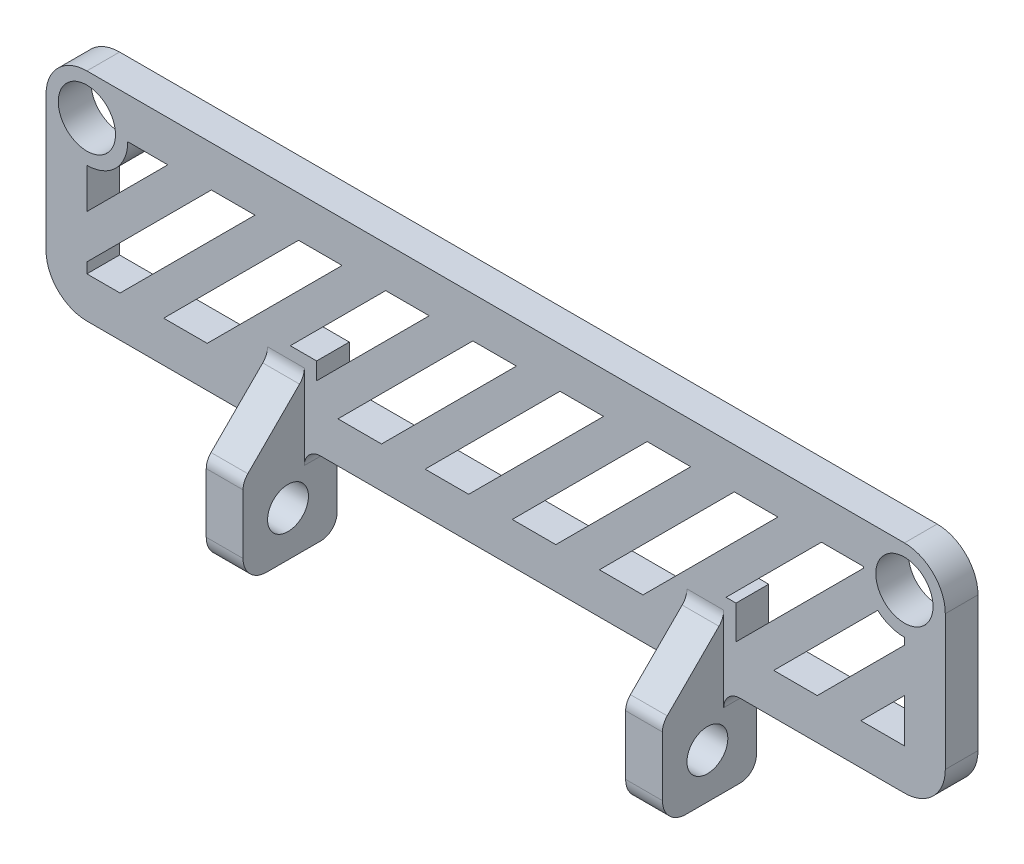
SolidWorks part; units mm, degrees
ref_plane "Plan de face" through (0, 0, 0) normal (0, 0, 1) x (1, 0, 0)
ref_plane "Plan de dessus" through (0, 0, 0) normal (0, 1, 0) x (1, 0, 0)
ref_plane "Plan de droite" through (0, 0, 0) normal (1, 0, 0) x (0, 0, -1)
sketch "Esquisse1" plane through (0, 0, 0) normal (0, 0, 1) x (1, 0, 0)
  line L0 (-25, 6.875) -> (-27.5, 6.875) construction
  line L1 (-27.5, 9.375) -> (27.5, 9.375)
  line L2 (-27.5, 9.375) -> (-27.5, -9.375)
  line L3 (-27.5, -9.375) -> (27.5, -9.375)
  line L4 (27.5, 9.375) -> (27.5, -9.375)
  line L5 (25, 6.875) -> (27.5, 6.875) construction
  line L6 (-25, 6.875) -> (-25, 9.375) construction
  line L7 (25, 6.875) -> (25, 9.375) construction
  line L8 (0, 0) -> (27.5, 0) construction
  line L9 (-13.95, -9.375) -> (-13.95, -3.875)
  line L10 (-13.95, -3.875) -> (13.95, -3.875)
  line L11 (13.95, -3.875) -> (13.95, -9.375)
  line L12 (-11.7, -3.875) -> (-11.7, -9.375)
  line L13 (11.7, -3.875) -> (11.7, -9.375)
  line L14 (-13.95, -6.625) -> (-11.7, -6.625) construction
  line L15 (11.7, -6.625) -> (13.95, -6.625) construction
  circle A0 centre (-25, 6.875) radius 1.75
  circle A1 centre (25, 6.875) radius 1.75
  circle A2 centre (-25, -6.875) radius 1.75 construction
  circle A3 centre (25, -6.875) radius 1.75 construction
  point P10 (-27.5, 0)
  point P13 (0, 9.375)
  point P25 (0, -3.875)
  dimension "D4" = 3.5
  dimension "D1" = 55
  dimension "D2" = 18.75
  dimension "D3" = 50
  dimension "D5" = 27.9
  dimension "D6" = 3
  dimension "D7" = 2.25
extrude "Boss.-Extru.1" add sketch "Esquisse1" along normal blind 2 contours L10 L11 L3 L4 L1 L2 L9 A2 A1 A0 A3 region at (0, 1.03, 0)
extrude "Boss.-Extru.3" add sketch "Esquisse1<3>" along normal blind 5.75 contours L12 L10 L9 L3 | L10 L13 L3 L11 region at (-12.825, -6.625, 0) region at (12.825, -6.625, 0)
sketch "Esquisse1<3>" plane through (0, 0, 0) normal (0, 0, 1) x (1, 0, 0) same geometry as "Esquisse1"
sketch "Esquisse2" plane through (13.95, 0, 0) normal (1, 0, 0) x (0, 0, -1)
  line L0 (-5.75, -3.875) -> (-5.75, -9.375) construction
  line L1 (-5.75, -9.375) -> (0, -9.375)
  line L2 (-5.75, -9.375) -> (-5.75, -3.875)
  line L3 (-5.75, -3.875) -> (0, -3.875)
  line L4 (0, -9.375) -> (0, -3.875)
  line L5 (-2, -9.375) -> (0, -9.375) construction
  line L6 (-2, -3.875) -> (-2, -9.375) construction
  line L7 (0, 9.375) -> (0, -9.375) construction
  circle A0 centre (-3, -6.625) radius 1.25
  point P7 (-2.875, -9.375)
  point P9 (0, -6.625)
  line M13 (-5.75, -9.375) -> (-2, -9.375)
  line M14 (-2, -9.375) -> (-2, -3.875)
  line M15 (-2, -3.875) -> (-5.75, -3.875)
  line M16 (-5.75, -3.875) -> (-5.75, -9.375)
  dimension "D2" = 2.5
  dimension "D1" = 5.5
  dimension "D3" = 1
extrude "Enlèv. mat.-Extru.4" cut sketch "Esquisse2" along normal up to next contours A0 M14 | A0 M14 M15 M16 M13 | A0 M14 | A0 L1 L4 L3 M14 region at (13.95, -6.625, 5.6834) region at (13.95, -6.625, 0.9786) region at (13.95, -6.625, 1.8991) region at (13.95, -6.625, 3.0604)
extrude "Enlèv. mat.-Extru.5" cut sketch "Esquisse2<5>" against normal up to next contours A0 M14 | A0 M14 region at (13.95, -6.625, 1.8991) region at (13.95, -6.625, 3.0604)
sketch "Esquisse2<5>" plane through (13.95, 0, 0) normal (1, 0, 0) x (0, 0, -1) same geometry as "Esquisse2"
sketch "Esquisse4" plane through (13.95, 0, 0) normal (1, 0, 0) x (0, 0, -1)
  line L0 (-5.75, -3.875) -> (-2, -0.125)
  line L1 (-2, 9.375) -> (-2, -3.875) construction
  line L2 (-5.75, -3.875) -> (-2, -3.875) construction
  line L3 (-2, -3.875) -> (-2, -0.125) construction
rib "Nervure1" sketch "Esquisse4" sketch "Esquisse4" thickness 2.25 extrusion direction parallel to sketch draft on no parameters "D1"=2.25
mirror "Symétrie2" about plane through (0, 0, 0) normal (1, 0, 0) of "Enlèv. mat.-Extru.4", "Enlèv. mat.-Extru.5", "Nervure1"
fillet "Congé1" radius 1.45 2 edges at (12.825, -9.375, 5.75) (-12.825, -9.375, 5.75)
fillet "Congé2" radius 1 10 edges at (12.825, -0.125, 2) (12.825, -3.875, 5.75) (13.95, -3.875, 1) (11.7, -3.875, 1) (12.825, -9.375, 0) (-12.825, -9.375, 0) (-13.95, -3.875, 1) (-11.7, -3.875, 1) (-12.825, -0.125, 2) (-12.825, -3.875, 5.75)
sketch "Esquisse5" plane through (0, 0, 2) normal (0, 0, 1) x (1, 0, 0)
  line L0 (-25, 6.875) -> (-27.5, 6.875) construction
  line L1 (-25, 6.875) -> (25, 6.875)
  line L2 (-25, 6.875) -> (-25, -1.375)
  line L3 (-25, -1.375) -> (25, -1.375)
  line L4 (25, 6.875) -> (25, -1.375)
  line L5 (-27.5, 9.375) -> (-27.5, -3.875) construction
  line L6 (25, 6.875) -> (27.5, 6.875) construction
  line L7 (27.5, 9.375) -> (27.5, -3.875) construction
  line L8 (25, -1.375) -> (25, -3.875) construction
  line L9 (27.5, -3.875) -> (14.95, -3.875) construction
  line L10 (-25, 1.9253) -> (-20.0503, 6.875)
  line L11 (-25, 6.875) -> (-22.5251, 4.4001) construction
  line L12 (-22.335, 1.9253) -> (-17.3852, 6.875)
  line L13 (-19.67, 1.9253) -> (-14.7202, 6.875)
  line L14 (-17.005, 1.9253) -> (-12.0552, 6.875)
  line L15 (-14.3399, 1.9253) -> (-9.3902, 6.875)
  line L16 (-11.6749, 1.9253) -> (-6.7252, 6.875)
  line L17 (-9.0099, 1.9253) -> (-4.0602, 6.875)
  line L18 (-6.3449, 1.9253) -> (-1.3952, 6.875)
  line L19 (-3.6799, 1.9253) -> (1.2698, 6.875)
  line L20 (-1.0149, 1.9253) -> (3.9349, 6.875)
  line L21 (1.6501, 1.9253) -> (6.5999, 6.875)
  line L22 (4.3151, 1.9253) -> (9.2649, 6.875)
  line L23 (6.9802, 1.9253) -> (11.9299, 6.875)
  line L24 (9.6452, 1.9253) -> (14.5949, 6.875)
  line L25 (12.3102, 1.9253) -> (17.2599, 6.875)
  line L26 (-27.665, 1.9253) -> (-22.7153, 6.875)
  line L27 (-22.5251, 4.4001) -> (-19.8601, 4.4001) construction
  line L28 (-25.1901, 4.4001) -> (-22.5251, 4.4001) construction
  line L29 (-27.5, 9.375) -> (27.5, 9.375) construction
  line L30 (13.95, -0.4179) -> (13.95, 0.2892) construction
  line L31 (28.3003, 1.9253) -> (33.25, 6.875) construction
  line L32 (25, -1.375) -> (28.3003, 1.9253) construction
  line L33 (-22.335, 1.9253) -> (-25, -0.7398)
  line L34 (-19.67, 1.9253) -> (-22.9702, -1.375)
  line L35 (-17.005, 1.9253) -> (-20.3052, -1.375)
  line L36 (-14.3399, 1.9253) -> (-17.6402, -1.375)
  line L37 (-11.6749, 1.9253) -> (-14.9752, -1.375)
  line L38 (-9.0099, 1.9253) -> (-12.3102, -1.375)
  line L39 (-6.3449, 1.9253) -> (-9.6452, -1.375)
  line L40 (-3.6799, 1.9253) -> (-6.9802, -1.375)
  line L41 (-1.0149, 1.9253) -> (-4.3151, -1.375)
  line L42 (1.6501, 1.9253) -> (-1.6501, -1.375)
  line L43 (4.3151, 1.9253) -> (1.0149, -1.375)
  line L44 (6.9802, 1.9253) -> (3.6799, -1.375)
  line L45 (9.6452, 1.9253) -> (6.3449, -1.375)
  line L46 (12.3102, 1.9253) -> (9.0099, -1.375)
  line L47 (14.9752, 1.9253) -> (11.6749, -1.375)
  line L48 (17.6402, 1.9253) -> (14.3399, -1.375)
  line L49 (20.3052, 1.9253) -> (17.005, -1.375)
  line L50 (22.9702, 1.9253) -> (19.67, -1.375)
  line L51 (25, 1.29) -> (22.335, -1.375)
  line L52 (14.9752, 1.9253) -> (19.9249, 6.875) [skipped]
  line L53 (17.6402, 1.9253) -> (22.5899, 6.875) [skipped]
  line L54 (20.3052, 1.9253) -> (25.255, 6.875) [skipped]
  line L55 (22.9702, 1.9253) -> (27.92, 6.875) [skipped]
  line L56 (25.6352, 1.9253) -> (30.585, 6.875) [skipped]
  line L61 (10.95, -1.375) -> (14.7, -1.375)
  line L62 (10.95, -1.375) -> (10.95, 1.0392)
  line L63 (10.95, 1.0392) -> (14.7, 1.0392)
  line L64 (14.7, -1.375) -> (14.7, 1.0392)
  line L65 (13.95, -0.4179) -> (14.7, -0.4179) construction
  line L66 (12.825, 0.2892) -> (12.825, 1.0392) construction
  line L67 (11.7, 0.2892) -> (13.95, 0.2892) construction
  line L68 (0, 0) -> (0, 0.2751) construction
  line L69 (-14.7, -1.375) -> (-14.7, 1.0392)
  line L70 (-10.95, 1.0392) -> (-14.7, 1.0392)
  line L71 (-10.95, -1.375) -> (-10.95, 1.0392)
  line L72 (11.7, -1.375) -> (11.7, 0.2892)
  line L73 (11.7, -3.5821) -> (11.7, -0.4179) construction
  line L74 (11.7, 0.2892) -> (13.95, 0.2892)
  line L75 (13.95, 0.2892) -> (13.95, -1.375)
  line L76 (13.95, -3.5821) -> (13.95, -0.4179) construction
  line L77 (14.9752, 1.9253) -> (19.9249, 6.875)
  line L78 (17.6402, 1.9253) -> (22.5899, 6.875)
  line L79 (20.3052, 1.9253) -> (23.3643, 4.9844)
  line L80 (22.9702, 1.9253) -> (25, 3.955)
  circle A0 centre (-25, 6.875) radius 2.5
  circle A1 centre (25, 6.875) radius 2.5
  dimension "D1" = 45
  dimension "D2" = 3.5
  dimension "D6" = 0.75
  dimension "D3" = 21
  dimension "D4" = 14
  dimension "D5" = 2
extrude "Enlèv. mat.-Extru.6" cut sketch "Esquisse5" against normal up to next contours A0 L2 L10 L1 | L34 L13 L1 L12 L33 L2 L3 | L36 L15 L1 L14 L35 L3 | L71 L38 L17 L1 L16 L37 L70 | L40 L19 L1 L18 L39 L3 | L42 L21 L1 L20 L41 L3 | L44 L23 L1 L22 L43 L3 | L62 L63 L46 L25 L1 L24 L45 L3 | L63 L62 L46 | A1 L1 L77 L47 L63 L64 L48 L78 | A1 L79 L49 L3 L50 L80 L4 | L4 L51 L3 region at (-22.9563, 4.8313, 2) region at (-20.1311, 2.7862, 2) region at (-14.8477, 2.75, 2) region at (-8.3895, 3.8444, 2) region at (-4.1877, 2.75, 2) region at (1.1424, 2.75, 2) region at (6.4724, 2.75, 2) region at (11.806, 2.7596, 2) region at (17.9856, 3.526, 2) region at (11.108, 0.8812, 2) region at (21.2644, 1.5819, 2) region at (24.1117, -0.4867, 2)
fillet "Congé4" radius 2.5 4 edges at (-27.5, -3.875, 1) (-27.5, 9.375, 1) (27.5, 9.375, 1) (27.5, -3.875, 1)
